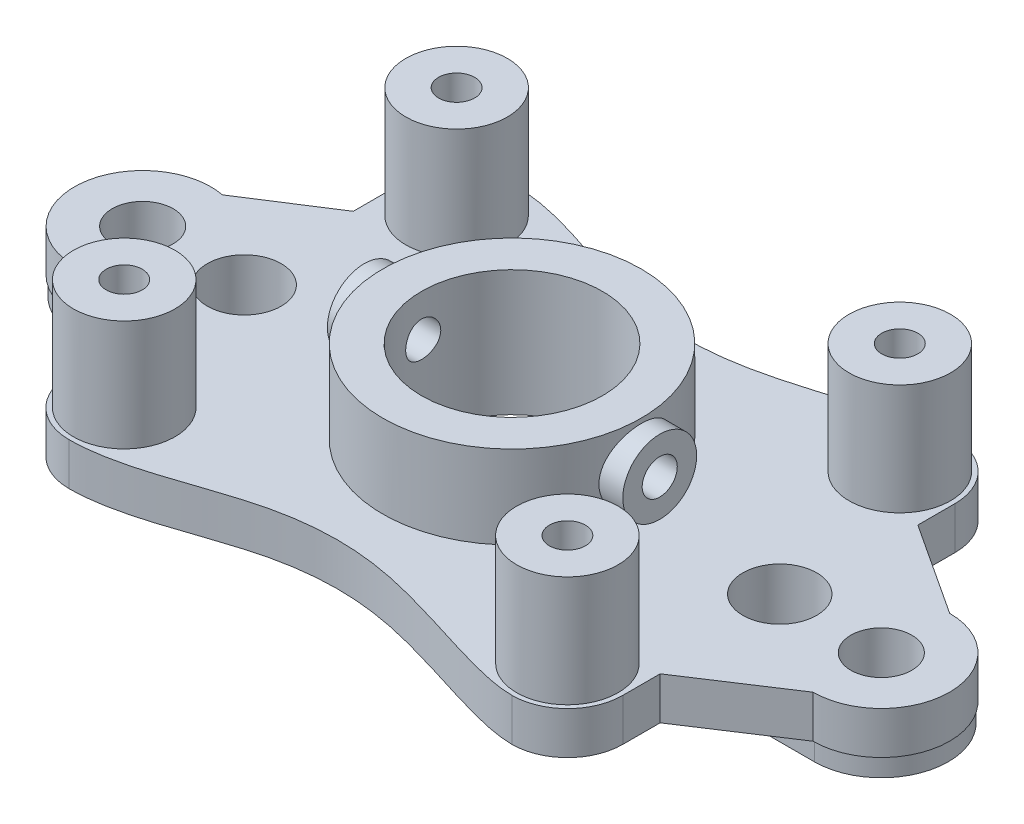
SolidWorks part; units mm, degrees
ref_plane "Front Plane" through (0, 0, 0) normal (0, 0, 1) x (1, 0, 0)
ref_plane "Top Plane" through (0, 0, 0) normal (0, 1, 0) x (1, 0, 0)
ref_plane "Right Plane" through (0, 0, 0) normal (1, 0, 0) x (0, 0, -1)
sketch "Sketch1" plane through (0, 0, 0) normal (0, 1, 0) x (1, 0, 0)
  line L0 (-24.5773, 0) -> (29.3366, 0) construction
  line L4 (0, 12.8011) -> (0, -15.3174) construction
  line L5 (-0.3815, -4.5531) -> (0, -4.9) construction
  line L6 (-19.3113, 3.6353) -> (-15, 6.4027)
  line L7 (20, -3.7) -> (15, -6.9768)
  line L8 (15, -12) -> (-15, -12)
  line L9 (15, -12) -> (15, -6.9768)
  line L10 (15, 12) -> (-15, 12)
  line L11 (-15, -12) -> (-15, -6.4027)
  line L12 (15, -12) -> (-15, 12) construction
  line L13 (15, 12) -> (-15, -12) construction
  line L15 (-15, 6.4027) -> (-15, 12)
  line L16 (15, 6.9768) -> (15, 12)
  line L17 (-19.3113, -3.6353) -> (-15, -6.4027)
  line L18 (20, 3.7) -> (15, 6.9768)
  circle A0 centre (0, 0) radius 4.9
  circle A1 centre (-20, 0) radius 1.65
  circle A2 centre (20, 0) radius 1.65
  arc A3 (-19.3113, -3.6353) -> (-19.3113, 3.6353) centre (-20, 0) cw
  arc A4 (20, -3.7) -> (20, 3.7) centre (20, 0) ccw
  point P5 (-20, 0)
  point P6 (20, 0)
  point P21 (13.5, 0)
  point P30 (-13.5, 0)
  dimension "D3" = 9.8
  dimension "D4" = 1.65
  dimension "D5" = 1.65
  dimension "D6" = 3.7
  dimension "D7" = 3.7
  dimension "D8" = 30
  dimension "D1" = 20
  dimension "D2" = 20
  dimension "D9" = 13.5
  dimension "D10" = 13.5
  dimension "D11" = 24
extrude "Boss-Extrude1" add sketch "Sketch1" along normal blind 2.3
fillet "Fillet1" radius 3 4 edges at (-15, 1.15, 12) (15, 1.15, 12) (15, 1.15, -12) (-15, 1.15, -12)
sketch "Sketch3" plane through (0, 2.3, 0) normal (0, 1, 0) x (1, 0, 0)
  line L1 (12, -9) -> (-12, -9) construction
  line L2 (12, -9) -> (12, 9) construction
  line L3 (12, 9) -> (-12, 9) construction
  line L4 (-12, -9) -> (-12, 9) construction
  line L5 (12, -9) -> (-12, 9) construction
  line L6 (12, 9) -> (-12, -9) construction
  circle A0 centre (-12, 9) radius 2.75
  circle A1 centre (12, 9) radius 2.75
  circle A2 centre (12, -9) radius 2.75
  circle A3 centre (-12, -9) radius 2.75
  circle A4 centre (-12, 9) radius 0.975
  circle A5 centre (12, 9) radius 0.975
  circle A6 centre (12, -9) radius 0.975
  circle A7 centre (-12, -9) radius 0.975
  point P0 (0, 0)
  dimension "D3" = 5.5
  dimension "D4" = 5.5
  dimension "D5" = 5.5
  dimension "D6" = 5.5
  dimension "D7" = 1.95
  dimension "D8" = 1.95
  dimension "D9" = 1.95
  dimension "D10" = 1.95
  dimension "D1" = 18
  dimension "D2" = 24
extrude "Boss-Extrude2" add sketch "Sketch3" along normal blind 6
sketch "Sketch4" plane through (0, 2.3, 0) normal (0, 1, 0) x (1, 0, 0)
  line L0 (12, 12) -> (-12, 12) construction
  line L2 (-12, 12) -> (-12, 16.2943)
  line L3 (-12, 16.2943) -> (12, 16.2943)
  line L4 (12, 16.2943) -> (12, 15.2199)
  line L5 (12, 15.2199) -> (12, 12)
  line L6 (-2.751, 0) -> (3.3044, 0) construction
  line L7 (12, -16.2943) -> (12, -15.2199)
  line L8 (-12, -16.2943) -> (12, -16.2943)
  line L9 (-12, -12) -> (-12, -16.2943)
  line L10 (12, -15.2199) -> (12, -12)
  spline S0 degree 3 poles (-12, 12) (-9.0572, 12) (-4.224, 9.4286) (3.7646, 9.2381) (9.8142, 12) (12, 12) knots 0 0 0 0 0.370531 0.6105 1 1 1 1
  spline S1 degree 3 poles (-12, -12) (-9.0572, -12) (-4.224, -9.4286) (3.7646, -9.2381) (9.8142, -12) (12, -12) knots 0 0 0 0 0.370531 0.6105 1 1 1 1
extrude "Cut-Extrude1" cut sketch "Sketch4" against normal up to surface (2.3 mm away) up to face at (20, 0, 1.65)
sketch "Sketch5" plane through (0, 2.3, 0) normal (0, 1, 0) x (1, 0, 0)
  circle A0 centre (0, 0) radius 4.9
  circle A1 centre (0, 0) radius 7
  dimension "D1" = 14
extrude "Boss-Extrude3" add sketch "Sketch5" along normal blind 4.5
sketch "Sketch6" plane through (0, 0, 0) normal (1, 0, 0) x (0, 0, -1)
  line L0 (0, 0) -> (0, 2.3) construction
  line L1 (0, 2.3) -> (0, 6.8) construction
  line L2 (4.9, 6.8) -> (-4.9, 6.8) construction
  circle A1 centre (0, 4.55) radius 2
  dimension "D2" = 4
extrude "Boss-Extrude4" add sketch "Sketch6" along normal blind 2 from offset 6
extrude "Boss-Extrude5" add sketch "Sketch6<2>" against normal blind 2 from offset 6 offset against normal yes
sketch "Sketch6<2>" plane through (0, 0, 0) normal (1, 0, 0) x (0, 0, -1) same geometry as "Sketch6"
sketch "Sketch7" plane through (8, 0, 0) normal (1, 0, 0) x (0, 0, -1)
  circle A0 centre (-18.0778, 8.3615) radius 0.1048
  circle A1 centre (0, 4.55) radius 0.95
  dimension "D1" = 1.9
extrude "Cut-Extrude2" cut sketch "Sketch7" against normal up to surface (16 mm away) up to face at (-8, 4.55, -2)
sketch "Sketch8" plane through (0, 2.3, 0) normal (0, 1, 0) x (1, 0, 0)
  line L0 (-20, 0) -> (-14.5, 0) construction
  line L1 (20, 0) -> (14.5, 0) construction
  circle A0 centre (-14.5, 0) radius 2
  circle A1 centre (14.5, 0) radius 2
  dimension "D1" = 5.5
  dimension "D2" = 5.5
extrude "Cut-Extrude3" cut sketch "Sketch8" against normal up to surface (2.3 mm away) up to face at (0.043, 0, 0)
sketch "Sketch10" plane through (0, 0, 0) normal (0, -1, 0) x (1, 0, 0)
  line L0 (-14.5, 2) -> (-14.5, -2) construction
  line L1 (14.5, 2) -> (14.5, -2) construction
  line L2 (-20, 1.65) -> (-20, -1.65) construction
  line L3 (20, 1.65) -> (20, -1.65) construction
  line L4 (-20, 0) -> (-14.5, 0) construction
  line L5 (-20, 3.63) -> (-14.5, 3.63)
  line L6 (-20, -3.63) -> (-14.5, -3.63)
  line L7 (14.5, 0) -> (20, 0) construction
  line L8 (14.5, 3.63) -> (20, 3.63)
  line L9 (14.5, -3.63) -> (20, -3.63)
  circle A0 centre (-14.5, 0) radius 2 construction
  circle A1 centre (14.5, 0) radius 2 construction
  circle A2 centre (-14.5, 0) radius 2
  circle A4 centre (14.5, 0) radius 2
  circle A6 centre (-20, 0) radius 1.65 construction
  circle A7 centre (20, 0) radius 1.65 construction
  circle A8 centre (-20, 0) radius 1.65
  circle A10 centre (20, 0) radius 1.65
  arc A11 (-20, 3.63) -> (-20, -3.63) centre (-20, 0) ccw
  arc A12 (-14.5, -3.63) -> (-14.5, 3.63) centre (-14.5, 0) ccw
  arc A13 (14.5, 3.63) -> (14.5, -3.63) centre (14.5, 0) ccw
  arc A14 (20, -3.63) -> (20, 3.63) centre (20, 0) ccw
  point P28 (-17.25, 0)
  point P33 (17.25, 0)
  dimension "D1" = 3.63
  dimension "D2" = 3.63
extrude "Boss-Extrude8" add sketch "Sketch10" along normal blind 1
